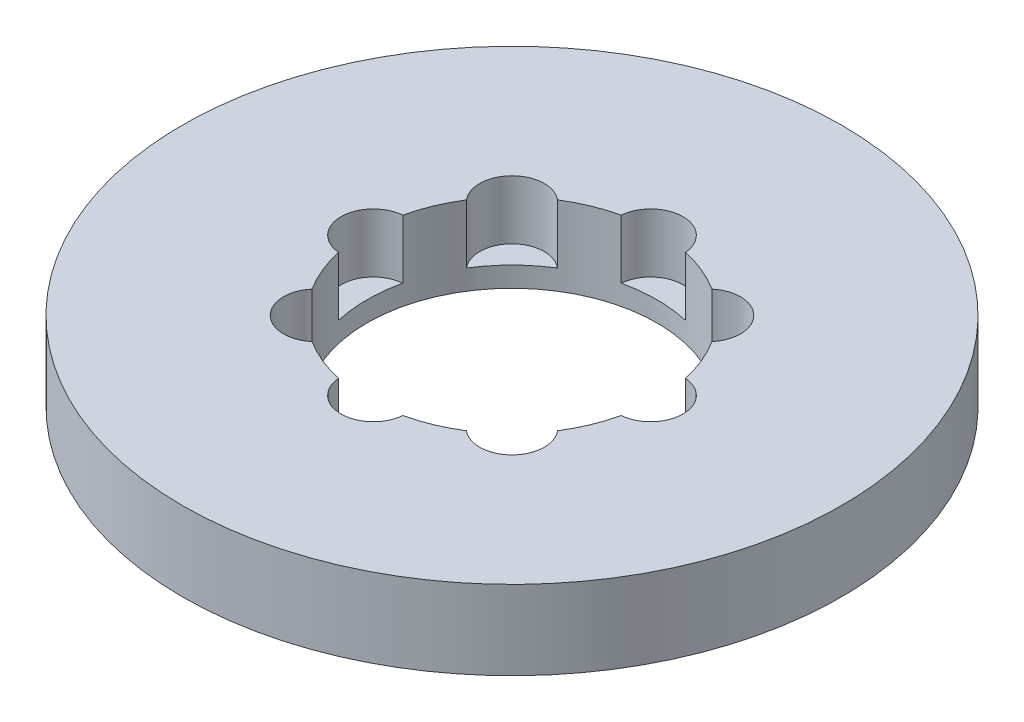
SolidWorks part; units mm, degrees
ref_plane "Front Plane" through (0, 0, 0) normal (0, 0, 1) x (1, 0, 0)
ref_plane "Top Plane" through (0, 0, 0) normal (0, 1, 0) x (1, 0, 0)
ref_plane "Right Plane" through (0, 0, 0) normal (1, 0, 0) x (0, 0, -1)
sketch "Sketch1" plane through (0, 0, 0) normal (0, 1, 0) x (1, 0, 0)
  circle A0 centre (0, 0) radius 62.5
  dimension "FLANGE_OD" = 125
extrude "Boss-Extrude1" add sketch "Sketch1" along normal blind 15
sketch "Sketch2" plane through (0, 0, 0) normal (0, 1, 0) x (1, 0, 0)
  circle A0 centre (0, 0) radius 27.5
  dimension "BORE_D" = 55
extrude "Cut-Extrude1" cut sketch "Sketch2" along normal through all
sketch "Sketch3" plane through (0, 15, 0) normal (0, 1, 0) x (1, 0, 0)
  circle A0 centre (0, 0) radius 26.301 construction
  circle A1 centre (-26.301, 0) radius 6.1244
  dimension "BOLT_D" = 12.2489
  dimension "BOLT_PCD" = 52.602
extrude "Cut-Extrude2" cut sketch "Sketch3" against normal blind 11.1812
pattern_circular "CirPattern1" count 8 over 360 about axis through (0, 0, 0) along (0, 1, 0) of "Cut-Extrude2"
